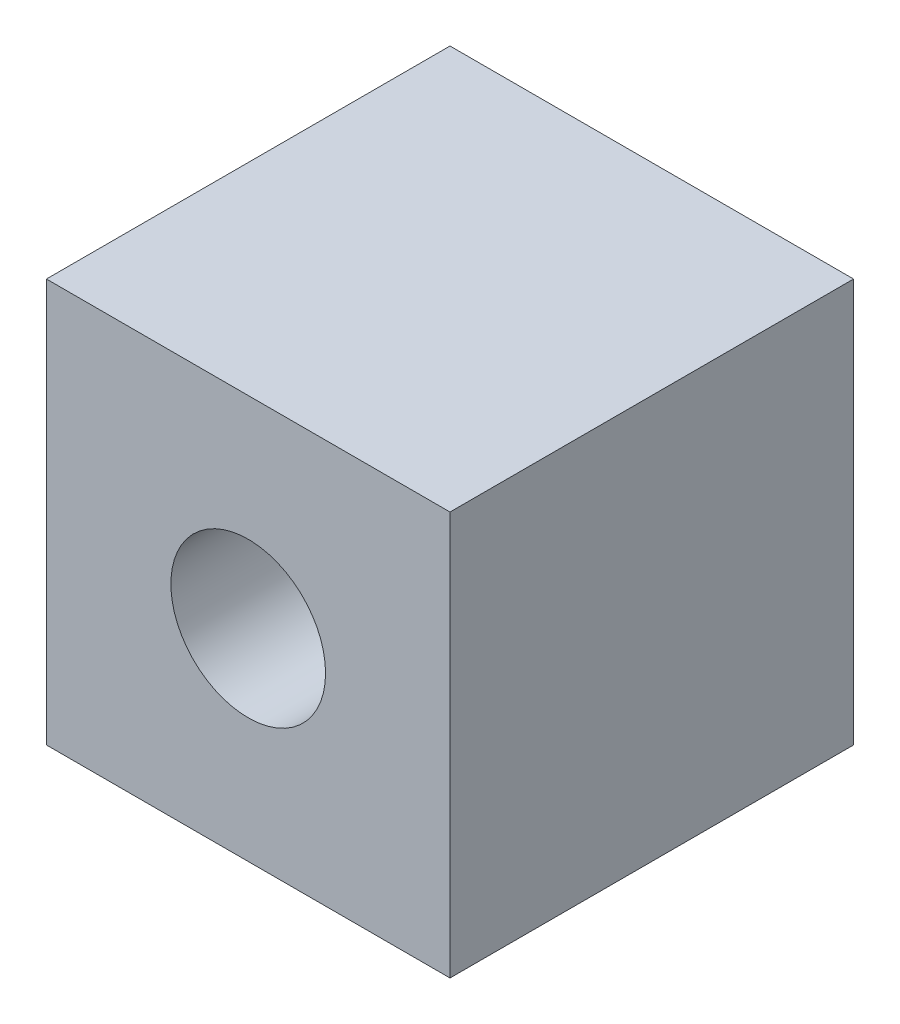
SolidWorks part; units mm, degrees
ref_plane "正面" through (0, 0, 0) normal (0, 0, 1) x (1, 0, 0)
ref_plane "平面" through (0, 0, 0) normal (0, 1, 0) x (1, 0, 0)
ref_plane "右側面" through (0, 0, 0) normal (1, 0, 0) x (0, 0, -1)
sketch "ｽｹｯﾁ1" plane through (0, 0, 0) normal (0, 0, 1) x (1, 0, 0)
  line L1 (-2.7788, 2.893) -> (3.2212, 2.893)
  line L2 (-2.7788, 2.893) -> (-2.7788, -3.107)
  line L3 (-2.7788, -3.107) -> (3.2212, -3.107)
  line L4 (3.2212, 2.893) -> (3.2212, -3.107)
  dimension "D1" = 6
  dimension "D2" = 6
extrude "ﾎﾞｽ - 押し出し1" add sketch "ｽｹｯﾁ1" along normal blind 6
sketch "ｽｹｯﾁ2" plane through (0, 0, 6) normal (0, 0, 1) x (1, 0, 0)
  line L0 (3.2212, 2.893) -> (-2.7788, 2.893) construction
  line L1 (-2.7788, 2.893) -> (-2.7788, -3.107) construction
  circle A0 centre (0.2212, -0.107) radius 1.15
  dimension "D1" = 2.3
  dimension "D2" = 3
  dimension "D3" = 3
extrude "ｶｯﾄ - 押し出し1" cut sketch "ｽｹｯﾁ2" against normal through all
